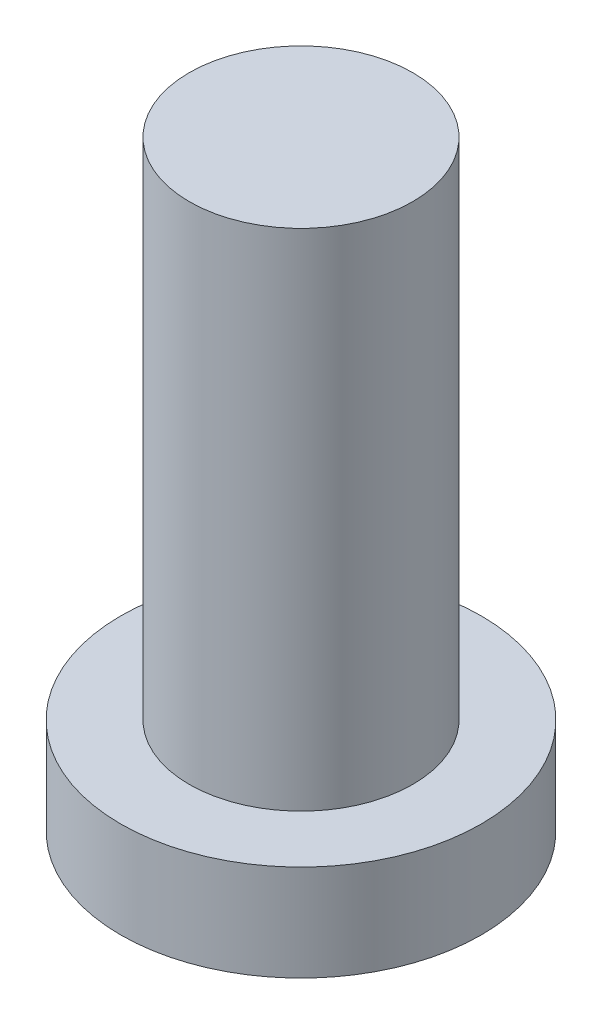
SolidWorks part; units mm, degrees
ref_plane "Front Plane" through (0, 0, 0) normal (0, 0, 1) x (1, 0, 0)
ref_plane "Top Plane" through (0, 0, 0) normal (0, 1, 0) x (1, 0, 0)
ref_plane "Right Plane" through (0, 0, 0) normal (1, 0, 0) x (0, 0, -1)
sketch "Sketch1" plane through (0, 0, 0) normal (0, 1, 0) x (1, 0, 0)
  circle A0 centre (0, 0) radius 7.5
  dimension "D1" = 15
extrude "Boss-Extrude3" add sketch "Sketch1" along normal blind 4
sketch "Sketch4" plane through (0, 4, 0) normal (0, 1, 0) x (1, 0, 0)
  circle A0 centre (0, 0) radius 4.65
  dimension "D1" = 9.3
extrude "Boss-Extrude4" add sketch "Sketch4" along normal blind 21
